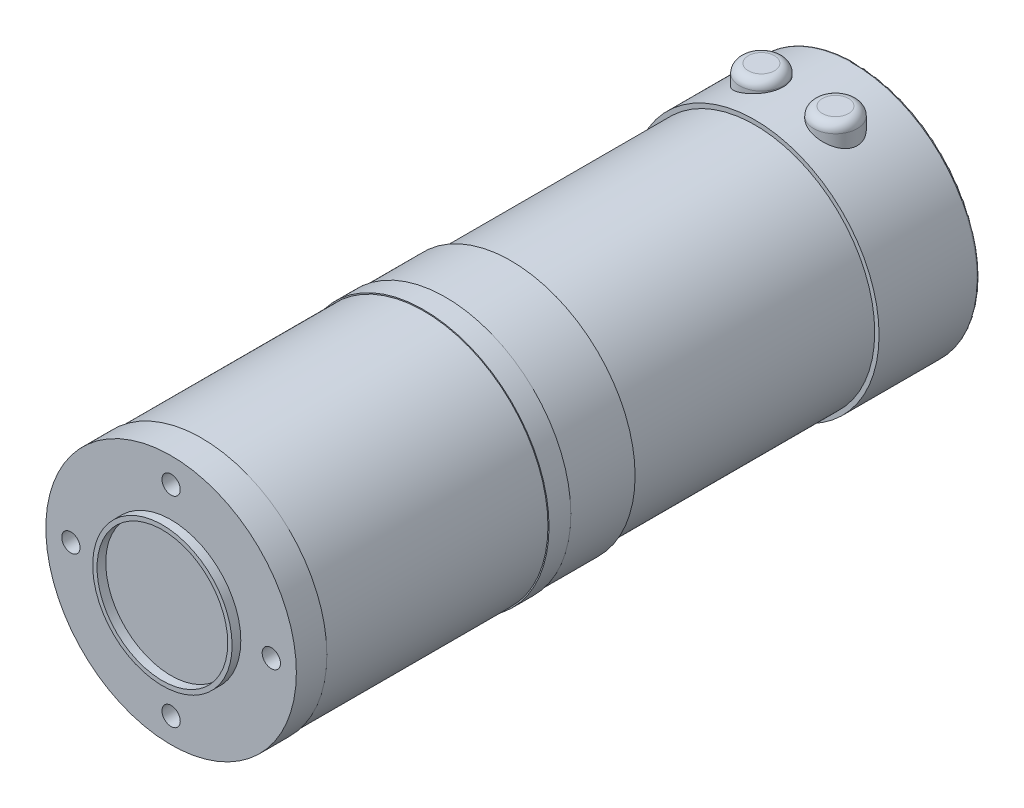
SolidWorks part; units mm, degrees
ref_plane "Plan de face" through (0, 0, 0) normal (0, 0, 1) x (1, 0, 0)
ref_plane "Plan de dessus" through (0, 0, 0) normal (0, 1, 0) x (1, 0, 0)
ref_plane "Plan de droite" through (0, 0, 0) normal (1, 0, 0) x (0, 0, -1)
sketch "Esquisse1" plane through (0, 0, 0) normal (0, 0, 1) x (1, 0, 0)
  circle A0 centre (0, 0) radius 28.5
  dimension "D1" = 57
extrude "Boss.-Extru.1" add sketch "Esquisse1" along normal blind 23
sketch "Esquisse3" plane through (0, 0, 23) normal (0, 0, 1) x (1, 0, 0)
  circle A0 centre (0, 0) radius 27.5
  dimension "D1" = 55
extrude "Boss.-Extru.2" add sketch "Esquisse3" along normal blind 56
sketch "Esquisse4" plane through (0, 0, 79) normal (0, 0, 1) x (1, 0, 0)
  circle A0 centre (0, 0) radius 28.5
  dimension "D1" = 57
extrude "Boss.-Extru.3" add sketch "Esquisse4" along normal blind 15
sketch "Esquisse5" plane through (0, 0, 94) normal (0, 0, 1) x (1, 0, 0)
  circle A0 centre (0, 0) radius 28.75
  dimension "D1" = 57.5
extrude "Boss.-Extru.4" add sketch "Esquisse5" along normal blind 5
sketch "Esquisse6" plane through (0, 0, 99) normal (0, 0, 1) x (1, 0, 0)
  circle A0 centre (0, 0) radius 28.5
  dimension "D1" = 57
extrude "Boss.-Extru.5" add sketch "Esquisse6" along normal blind 51
sketch "Esquisse7" plane through (0, 0, 150) normal (0, 0, 1) x (1, 0, 0)
  circle A0 centre (0, 0) radius 28.75
  circle A1 centre (0, 0) radius 28.75 construction
extrude "Boss.-Extru.6" add sketch "Esquisse7" along normal blind 7
fillet "Congé1" radius 0.5 1 edges at (28.5, 0, 0)
sketch "Esquisse8" plane through (0, 0, 157) normal (0, 0, 1) x (1, 0, 0)
  circle A0 centre (0, 0) radius 16
  circle A1 centre (0, 0) radius 15
  dimension "D1" = 32
  dimension "D2" = 1
extrude "Boss.-Extru.7" add sketch "Esquisse8" along normal blind 2
ref_axis "Axe1" through (0, 0, 157) along (0, 0, -1)
hole_wizard "Trou pour taraudage pour trou taraudé M51" positions "Esquisse11" profile "Esquisse10" hole size "M5" standard "ISO"
sketch "Esquisse11" plane through (0, 0, 157) normal (0, 0, 1) x (1, 0, 0)
  line L0 (37.9804, 0) -> (-44.7752, 0) construction
  circle A0 centre (0, 0) radius 23 construction
  point P0 (-23, 0)
  dimension "D1" = 46
sketch "Esquisse10" plane through (-23, 0, 157) normal (1, 0, 0) x (0, -1, 0)
  line L0 (0, 0) -> (0, 11.2618)
  line L1 (0, 11.2618) -> (2.1, 10)
  line L2 (2.1, 10) -> (2.1, 0)
  line L5 (2.1, 0) -> (0, 0)
  line L10 (0, 11.2618) -> (-2.1, 10) construction
  line L11 (0, -6.35) -> (0, 107.95) construction
  dimension "Diamètre du perçage" = 4.2
  dimension "Profondeur du perçage" = 10
  dimension "Angle de pointe" = 118
pattern_circular "Répétition circulaire1" count 4 over 360 about axis through (0, 0, 157) along (0, 0, -1) of "Trou pour taraudage pour trou taraudé M51"
ref_plane "Plan1" through (0, 28.5, 0) normal (0, 1, 0) x (1, 0, 0)
sketch "Esquisse12" plane through (0, 28.5, 0) normal (0, 1, 0) x (1, 0, 0)
  line L0 (0, 17.0258) -> (0, -64.3391) construction
  line L1 (-45.9766, -13) -> (54.5212, -13) construction
  line L2 (28, 0) -> (-28, 0) construction
  circle A0 centre (-8.5, -13) radius 5
  circle A1 centre (8.5, -13) radius 5
  dimension "D3" = 10
  dimension "D1" = 13
  dimension "D2" = 17
extrude "Boss.-Extru.8" add sketch "Esquisse12" along normal blind 2 and the other way blind 10
fillet "Congé2" radius 2 2 edges at (8.5, 30.5, 18) (-8.5, 30.5, 18)
